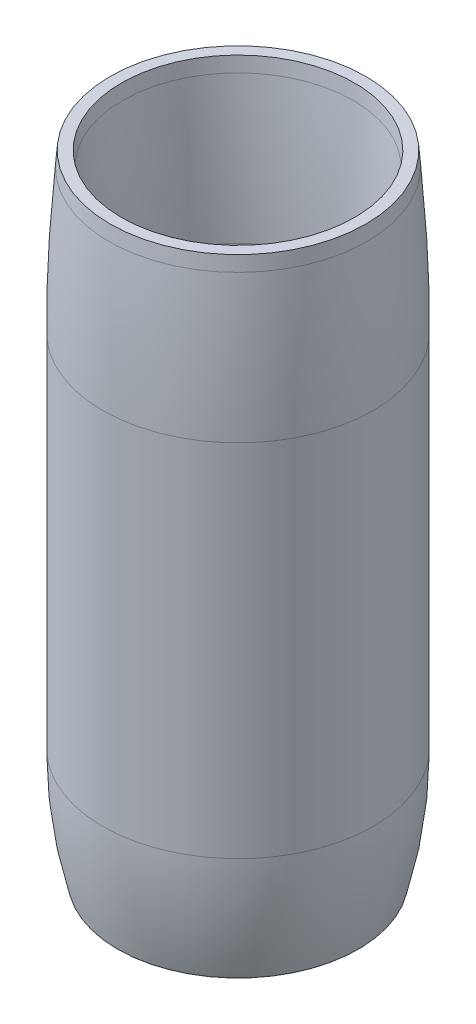
SolidWorks part; units mm, degrees
material "Nylon 101"
ref_plane "Front Plane" through (0, 0, 0) normal (0, 0, 1) x (1, 0, 0)
ref_plane "Top Plane" through (0, 0, 0) normal (0, 1, 0) x (1, 0, 0)
ref_plane "Right Plane" through (0, 0, 0) normal (1, 0, 0) x (0, 0, -1)
sketch "Sketch1" plane through (0, 0, 0) normal (0, 1, 0) x (1, 0, 0)
  circle A0 centre (0, 0) radius 4.5
  dimension "D1" = 9
extrude "Boss-Extrude1" add sketch "Sketch1" along normal blind 1
sketch "Sketch2" plane through (0, 1, 0) normal (0, 1, 0) x (1, 0, 0)
  circle A0 centre (0, 0) radius 3.625
  circle A1 centre (0, 0) radius 4.5
  circle A2 centre (0, 0) radius 4.5
  dimension "D2" = 7.25
  dimension "D1" = 0
extrude "Boss-Extrude2" add sketch "Sketch2" along normal blind 20
chamfer "Chamfer1" distance 0.5 angle 75 1 edges at (0, 0, 4.5) first distance on face at (0, 0, 4.5)
fillet "Fillet1" radius 14.6 1 edges at (0, 1.866, 4.5)
chamfer "Chamfer2" distance 0.25 angle 85 1 edges at (0, 21, 3.625) first distance on face at (0, 21, 4.5)
fillet "Fillet2" radius 54.6 1 edges at (0, 18.1425, 3.625)
chamfer "Chamfer3" distance 0.25 angle 85 1 edges at (0, 21, 4.5) first distance on face at (0, 21, 3.875)
fillet "Fillet3" radius 54.6 1 edges at (0, 18.1425, 4.5)
